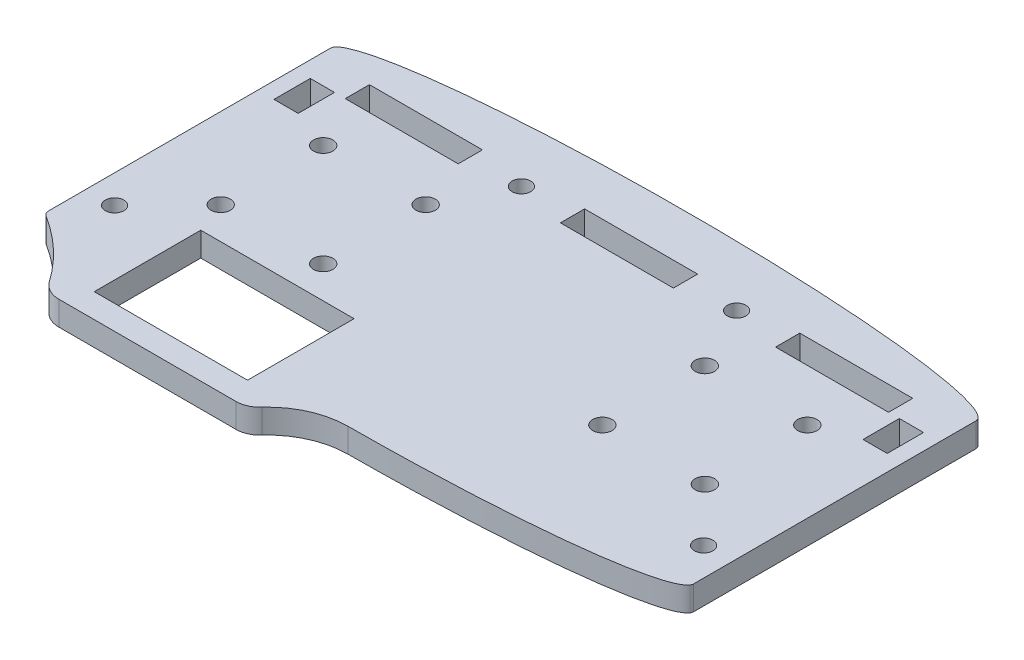
SolidWorks part; units mm, degrees
ref_plane "Front Plane" through (0, 0, 0) normal (0, 0, 1) x (1, 0, 0)
ref_plane "Top Plane" through (0, 0, 0) normal (0, 1, 0) x (1, 0, 0)
ref_plane "Right Plane" through (0, 0, 0) normal (1, 0, 0) x (0, 0, -1)
sketch "Sketch1" plane through (0, 0, 0) normal (0, 1, 0) x (1, 0, 0)
  line L1 (40, 17.5) -> (-40, 17.5)
  line L2 (40, 17.5) -> (40, -17.5)
  line L3 (40, -17.5) -> (-40, -17.5)
  line L4 (-40, 17.5) -> (-40, -17.5)
  line L5 (40, 17.5) -> (-40, -17.5) construction
  line L6 (40, -17.5) -> (-40, 17.5) construction
  point P0 (0, 0)
  dimension "D1" = 35
  dimension "D2" = 80
extrude "Boss-Extrude1" add sketch "Sketch1" along normal mid plane 3
sketch "Sketch2" plane through (0, 1.5, 0) normal (0, 1, 0) x (1, 0, 0)
  line L0 (-33.6667, 16) -> (-33.6667, 13) construction
  line L1 (-19.6667, 16) -> (-33.6667, 16) construction
  line L2 (-33.6667, 13) -> (-19.6667, 13) construction
  line L3 (-19.6667, 13) -> (-19.6667, 16) construction
  line L4 (-7, 16) -> (-7, 13) construction
  line L5 (7, 16) -> (-7, 16) construction
  line L6 (-7, 13) -> (7, 13) construction
  line L7 (7, 13) -> (7, 16) construction
  line L8 (19.6667, 16) -> (19.6667, 13) construction
  line L9 (33.6667, 16) -> (19.6667, 16) construction
  line L10 (19.6667, 13) -> (33.6667, 13) construction
  line L11 (33.6667, 13) -> (33.6667, 16) construction
  line L12 (-33.6667, 16) -> (-33.6667, 13)
  line L13 (-19.6667, 16) -> (-33.6667, 16)
  line L14 (-33.6667, 13) -> (-19.6667, 13)
  line L15 (-19.6667, 13) -> (-19.6667, 16)
  line L16 (-7, 16) -> (-7, 13)
  line L17 (7, 16) -> (-7, 16)
  line L18 (-7, 13) -> (7, 13)
  line L19 (7, 13) -> (7, 16)
  line L20 (19.6667, 16) -> (19.6667, 13)
  line L21 (33.6667, 16) -> (19.6667, 16)
  line L22 (19.6667, 13) -> (33.6667, 13)
  line L23 (33.6667, 13) -> (33.6667, 16)
  circle A0 centre (-13.3333, 14.5) radius 1.15 construction
  circle A1 centre (13.3333, 14.5) radius 1.15 construction
  circle A2 centre (-13.3333, 14.5) radius 1.15
  circle A3 centre (13.3333, 14.5) radius 1.15
extrude "Cut-Extrude1" cut sketch "Sketch2" against normal through all
sketch "Sketch3" plane through (0, 1.5, 0) normal (0, 1, 0) x (1, 0, 0)
  line L0 (40, 17.5) -> (-40, 17.5) construction
  line L1 (40, 17.5) -> (-40, 17.5)
  ellipse E0 centre (0, 17.5) end of major axis (-40, 17.5) minor radius 4.5 (40, 17.5) -> (-40, 17.5) ccw
  dimension "D1" = 4.5
extrude "Boss-Extrude2" add sketch "Sketch3" against normal up to vertex (3 mm away) up to point (40, -1.5, -17.5)
sketch "Sketch5" plane through (0, -1.5, 0) normal (0, -1, 0) x (1, 0, 0)
  line L0 (22.45, -6.6) -> (24.85, -6.6) construction
  line L1 (0, -6.6) -> (0, 8.833) construction
  line L2 (-28.16, -0.25) -> (-25.76, -0.25) construction
  line L3 (-28.16, 0.95) -> (-25.76, 0.95)
  line L4 (-28.16, -1.45) -> (-25.76, -1.45)
  line L5 (-24.85, 6.1) -> (-22.45, 6.1) construction
  line L6 (-24.85, 7.3) -> (-22.45, 7.3)
  line L7 (-24.85, 4.9) -> (-22.45, 4.9)
  line L8 (-22.45, -6.6) -> (-24.85, -6.6) construction
  line L9 (-22.45, -7.8) -> (-24.85, -7.8)
  line L10 (-22.45, -5.4) -> (-24.85, -5.4)
  line L11 (22.45, -5.4) -> (24.85, -5.4)
  line L12 (22.45, -7.8) -> (24.85, -7.8)
  line L13 (25.76, -0.25) -> (28.16, -0.25) construction
  line L14 (25.76, 0.95) -> (28.16, 0.95)
  line L15 (25.76, -1.45) -> (28.16, -1.45)
  line L16 (24.85, 6.1) -> (22.45, 6.1) construction
  line L17 (24.85, 4.9) -> (22.45, 4.9)
  line L18 (24.85, 7.3) -> (22.45, 7.3)
  circle A0 centre (-17.3, -6.6) radius 1.2
  circle A1 centre (-17.3, 6.1) radius 1.2
  circle A2 centre (-23.65, -6.6) radius 1.2 construction
  circle A3 centre (-23.65, 6.1) radius 1.2 construction
  circle A4 centre (-30, -6.6) radius 1.2
  circle A5 centre (-30, 6.1) radius 1.2
  circle A6 centre (-14.26, -0.25) radius 1.2
  circle A7 centre (-20.61, -0.25) radius 1.2
  circle A8 centre (-26.96, -0.25) radius 1.2 construction
  circle A9 centre (-33.31, -0.25) radius 1.2
  circle A10 centre (33.31, -0.25) radius 1.2
  circle A11 centre (26.96, -0.25) radius 1.2 construction
  circle A12 centre (20.61, -0.25) radius 1.2
  circle A13 centre (14.26, -0.25) radius 1.2
  circle A14 centre (30, 6.1) radius 1.2
  circle A15 centre (30, -6.6) radius 1.2
  circle A16 centre (23.65, 6.1) radius 1.2 construction
  circle A17 centre (23.65, -6.6) radius 1.2 construction
  circle A18 centre (17.3, 6.1) radius 1.2
  circle A19 centre (17.3, -6.6) radius 1.2
  arc A20 (-28.16, 0.95) -> (-28.16, -1.45) centre (-28.16, -0.25) ccw
  arc A21 (-25.76, -1.45) -> (-25.76, 0.95) centre (-25.76, -0.25) ccw
  arc A22 (-24.85, 7.3) -> (-24.85, 4.9) centre (-24.85, 6.1) ccw
  arc A23 (-22.45, 4.9) -> (-22.45, 7.3) centre (-22.45, 6.1) ccw
  arc A24 (-22.45, -7.8) -> (-22.45, -5.4) centre (-22.45, -6.6) ccw
  arc A25 (-24.85, -5.4) -> (-24.85, -7.8) centre (-24.85, -6.6) ccw
  arc A26 (22.45, -5.4) -> (22.45, -7.8) centre (22.45, -6.6) ccw
  arc A27 (24.85, -7.8) -> (24.85, -5.4) centre (24.85, -6.6) ccw
  arc A28 (25.76, 0.95) -> (25.76, -1.45) centre (25.76, -0.25) ccw
  arc A29 (28.16, -1.45) -> (28.16, 0.95) centre (28.16, -0.25) ccw
  arc A30 (24.85, 4.9) -> (24.85, 7.3) centre (24.85, 6.1) ccw
  arc A31 (22.45, 7.3) -> (22.45, 4.9) centre (22.45, 6.1) ccw
  point P50 (-26.96, -0.25)
  point P59 (-23.65, 6.1)
  point P67 (-23.65, -6.6)
  point P73 (23.65, -6.6)
  point P78 (26.96, -0.25)
  point P85 (23.65, 6.1)
  dimension "D1" = 3
  dimension "D3" = 4
  dimension "D2" = 6.35
  dimension "D4" = 6.35
extrude "Cut-Extrude2" cut sketch "Sketch5" against normal through all contours A19 | A18 | A14 | A15 | A1 | A4 | A5 | A0 region at (-17.3, -1.5, 6.1) region at (-30, -1.5, -6.6) region at (-30, -1.5, 6.1) region at (30, -1.5, 6.1) region at (30, -1.5, -6.6) region at (17.3, -1.5, 6.1) region at (17.3, -1.5, -6.6)
sketch "Sketch7" plane through (0, -1.5, 0) normal (0, -1, 0) x (1, 0, 0)
  line L0 (-36.5, 11.6) -> (-36.5, 13.9) construction
  line L1 (35, -8.5) -> (38, -8.5)
  line L2 (35, -8.5) -> (35, -13)
  line L3 (35, -13) -> (38, -13)
  line L4 (38, -8.5) -> (38, -13)
  line L5 (-35, -8.5) -> (-38, -8.5)
  line L6 (-35, -8.5) -> (-35, -13)
  line L7 (-35, -13) -> (-38, -13)
  line L8 (-38, -8.5) -> (-38, -13)
  line L9 (-35, 11.6) -> (-38, 11.6) construction
  line L10 (-35, 13.9) -> (-38, 13.9) construction
  line L11 (36.5, 13.9) -> (36.5, 11.6) construction
  line L12 (38, 13.9) -> (35, 13.9) construction
  line L13 (38, 11.6) -> (35, 11.6) construction
  circle A0 centre (-36.5, 12.75) radius 1.15
  circle A1 centre (36.5, 12.75) radius 1.15
extrude "Cut-Extrude3" cut sketch "Sketch7" against normal through all
sketch "Sketch8" plane through (0, -1.5, 0) normal (0, -1, 0) x (1, 0, 0)
  line L0 (-40, 17.5) -> (40, 17.5) construction
  line L1 (-40, 17.5) -> (40, 17.5)
  ellipse E0 centre (0, 17.5) end of major axis (40, 17.5) minor radius 4.5 (40, 17.5) -> (-40, 17.5) ccw
  dimension "D1" = 4.5
extrude "Boss-Extrude3" add sketch "Sketch8" against normal up to vertex (3 mm away) up to point (40, 1.5, 17.5)
sketch "Sketch10" plane through (0, 1.5, 0) normal (0, 1, 0) x (1, 0, 0)
  line L0 (-31.5, -20.2734) -> (-31.5, -26.2734)
  line L1 (-28.5, -10.0734) -> (-9.5, -10.0734)
  line L2 (-28.5, -10.0734) -> (-28.5, -23.2734)
  line L3 (-28.5, -23.2734) -> (-9.5, -23.2734)
  line L4 (-9.5, -10.0734) -> (-9.5, -23.2734)
  line L5 (-28.5, -10.0734) -> (-9.5, -23.2734) construction
  line L6 (-28.5, -23.2734) -> (-9.5, -10.0734) construction
  line L7 (-31.5, -26.2734) -> (-6.5, -26.2734)
  line L8 (-6.5, -26.2734) -> (-6.5, -21.9402)
  line L9 (-9.5, -23.2734) -> (-6.5, -23.2734) construction
  line L10 (-9.5, -23.2734) -> (-9.5, -26.2734) construction
  line L11 (-28.5, -23.2734) -> (-31.5, -23.2734) construction
  line L12 (-31.5, -12.75) -> (-31.5, -20.2734) construction
  line L13 (-36.5, -12.75) -> (-31.5, -12.75) construction
  ellipse E0 centre (0, -17.5) end of major axis (40, -17.5) minor radius 4.5 (-40, -17.5) -> (40, -17.5) ccw construction
  ellipse E1 centre (0, -17.5) end of major axis (40, -17.5) minor radius 4.5 (-31.5, -20.2734) -> (-6.5, -21.9402) ccw
  point P0 (-19, -16.6734)
  ellipse M32 centre (0, -17.5) end of major axis (40, -17.5) minor radius 4.5 (-40, -17.5) -> (40, -17.5) ccw
  dimension "D1" = 19
  dimension "D2" = 13.2
  dimension "D3" = 3
  dimension "D4" = 5
extrude "Boss-Extrude4" add sketch "Sketch10" against normal up to vertex (3 mm away) contours L7 L8 L4 L3 L2 L0 M32 | L4 L2 L3 M32 region at (-19.5451, 1.5, 24.3925) region at (-20.0025, 1.5, 22.3025) up to point (40, -1.5, 17.5)
extrude "Cut-Extrude4" cut sketch "Sketch10<3>" against normal blind 10 contours L4 L1 L2 M32 | L4 L2 L3 M32 region at (-20.0025, 1.5, 22.3025) region at (-18.8338, 1.5, 15.7401)
sketch "Sketch10<3>" plane through (0, 1.5, 0) normal (0, 1, 0) x (1, 0, 0) same geometry as "Sketch10"
fillet "Fillet1" radius 25 1 edges
fillet "Fillet2" radius 10 1 edges
fillet "Fillet3" radius 3 2 edges at (-31.5, 0, 26.2734) (-6.5, 0, 26.2734)
